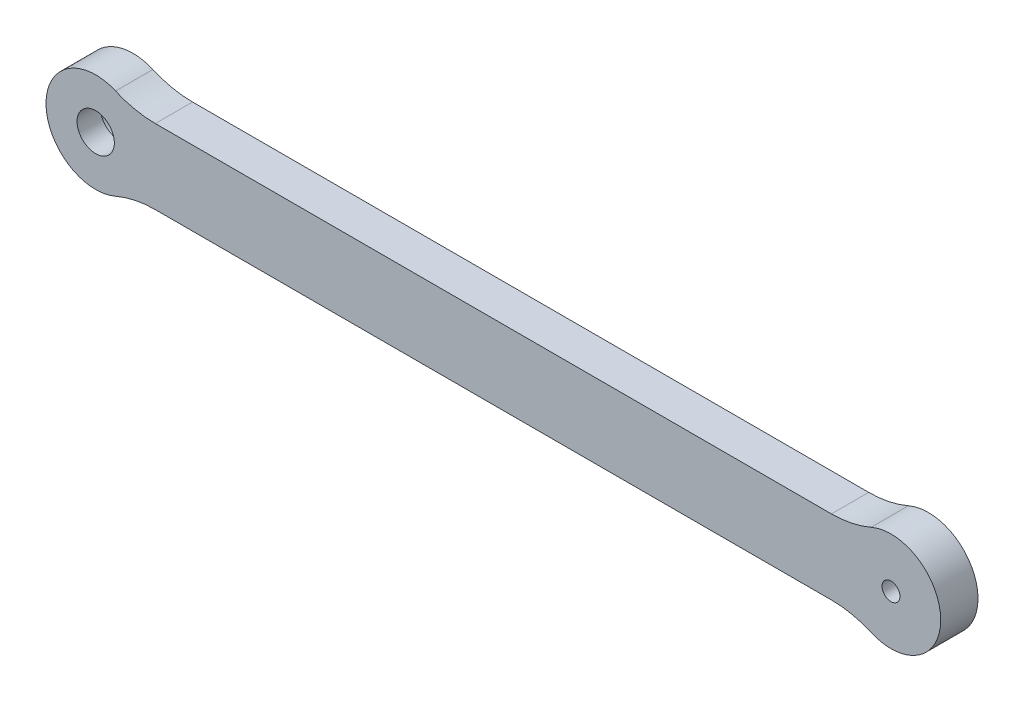
SolidWorks part; units mm, degrees
ref_plane "Front Plane" through (0, 0, 0) normal (0, 0, 1) x (1, 0, 0)
ref_plane "Top Plane" through (0, 0, 0) normal (0, 1, 0) x (1, 0, 0)
ref_plane "Right Plane" through (0, 0, 0) normal (1, 0, 0) x (0, 0, -1)
sketch "Sketch1" plane through (0, 0, 0) normal (0, 0, 1) x (1, 0, 0)
  line L0 (-187.9732, 9.525) -> (-15.2268, 9.525)
  line L1 (-187.9732, -9.525) -> (-15.2268, -9.525)
  arc A0 (-5.0756, -11.6417) -> (-5.0756, 11.6417) centre (0, 0) ccw
  arc A1 (-198.1244, 11.6417) -> (-198.1244, -11.6417) centre (-203.2, 0) ccw
  arc A2 (-198.1244, 11.6417) -> (-187.9732, 9.525) centre (-187.9732, 34.925) ccw
  arc A3 (-5.0756, 11.6417) -> (-15.2268, 9.525) centre (-15.2268, 34.925) cw
  arc A4 (-198.1244, -11.6417) -> (-187.9732, -9.525) centre (-187.9732, -34.925) cw
  arc A5 (-5.0756, -11.6417) -> (-15.2268, -9.525) centre (-15.2268, -34.925) ccw
  point P1 (0, 0)
  point P4 (0, 0)
  point P17 (0, 0)
  point P18 (0, 0)
  point P19 (-91.4743, 0)
  dimension "D2" = 12.7
  dimension "D3" = 25.4
  dimension "D1" = 19.05
  dimension "D4" = 203.2
extrude "Boss-Extrude1" add sketch "Sketch1" along normal blind 9.525
sketch "Sketch2" plane through (0, 0, 0) normal (0, 0, 1) x (1, 0, 0)
  circle A0 centre (-203.2, 0) radius 5.9944
  dimension "D1" = 11.9888
extrude "Cut-Extrude1" cut sketch "Sketch2" along normal blind 3.556
sketch "Sketch3" plane through (0, 0, 3.556) normal (0, 0, -1) x (-1, 0, 0)
  circle A0 centre (203.2, 0) radius 4.7625
  dimension "D1" = 9.525
extrude "Cut-Extrude2" cut sketch "Sketch3" against normal through all
sketch "Sketch4" plane through (0, 0, 9.525) normal (0, 0, 1) x (1, 0, 0)
  circle A0 centre (0, 0) radius 2.286
  dimension "D1" = 4.572
extrude "Cut-Extrude3" cut sketch "Sketch4" against normal through all
